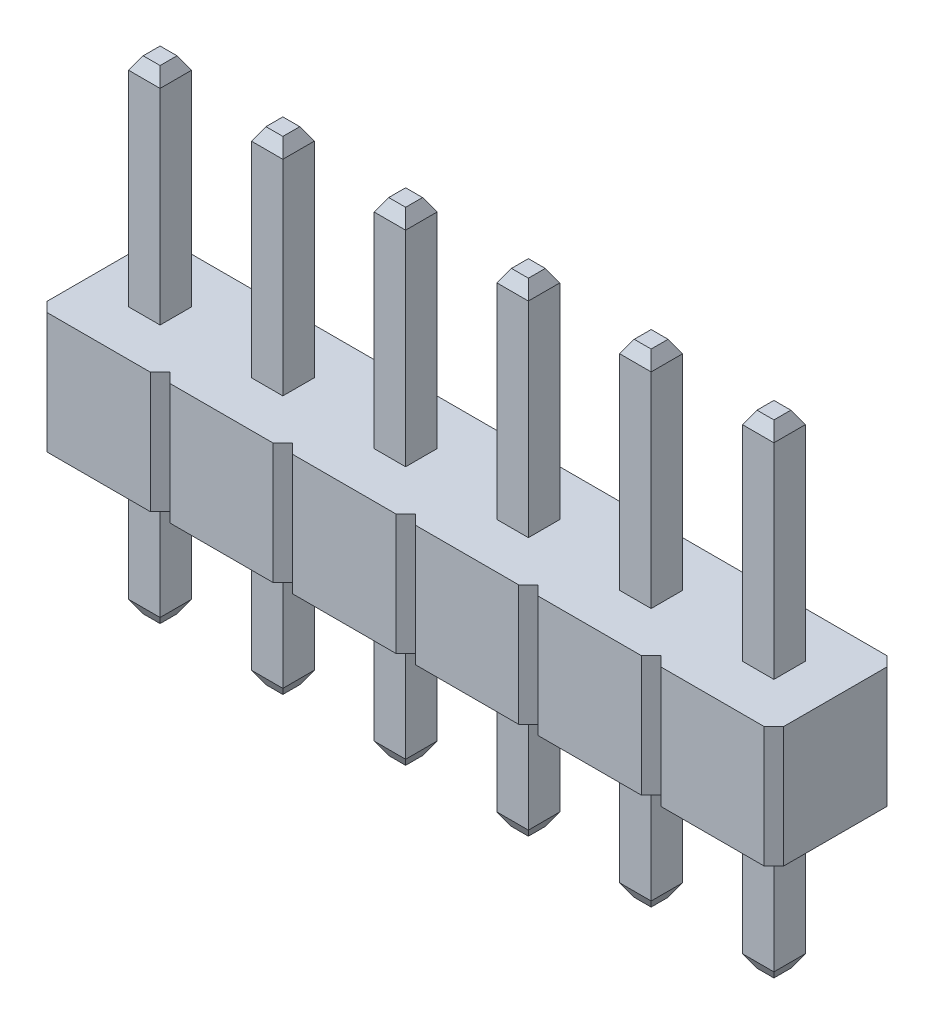
SolidWorks part; units mm, degrees
ref_plane "Front Plane" through (0, 0, 0) normal (0, 0, 1) x (1, 0, 0)
ref_plane "Top Plane" through (0, 0, 0) normal (0, 1, 0) x (1, 0, 0)
ref_plane "Right Plane" through (0, 0, 0) normal (1, 0, 0) x (0, 0, -1)
sketch "Sketch1" plane through (0, 0, 0) normal (0, 1, 0) x (1, 0, 0)
  line L0 (-7.42, 1.27) -> (-7.62, 1.07)
  line L1 (-7.62, 1.27) -> (7.62, 1.27) construction
  line L2 (-7.62, 1.27) -> (-7.62, -1.27) construction
  line L3 (-7.62, -1.27) -> (7.62, -1.27) construction
  line L4 (7.62, 1.27) -> (7.62, -1.27) construction
  line L5 (-7.62, 1.27) -> (7.62, -1.27) construction
  line L6 (-7.62, -1.27) -> (7.62, 1.27) construction
  line L7 (-5.28, -1.27) -> (-7.42, -1.27)
  line L8 (-5.08, -1.07) -> (-5.08, 1.07)
  line L9 (-5.28, 1.27) -> (-7.42, 1.27)
  line L10 (-7.62, -1.07) -> (-7.62, 1.07)
  line L11 (-5.08, -1.27) -> (-7.62, 1.27) construction
  line L12 (-5.08, 1.27) -> (-7.62, -1.27) construction
  line L13 (-5.08, 1.07) -> (-5.28, 1.27)
  line L14 (-7.42, -1.27) -> (-7.62, -1.07)
  line L15 (-5.08, -1.07) -> (-5.28, -1.27)
  point P0 (0, 0)
  point P6 (-6.35, 0)
  dimension "D1" = 15.24
  dimension "D2" = 2.54
extrude "Boss-Extrude1" add sketch "Sketch1" along normal blind 2.5
ref_plane "Plane1" through (0, -3, 0) normal (0, 1, 0) x (1, 0, 0)
sketch "Sketch3" plane through (0, -3, 0) normal (0, 1, 0) x (1, 0, 0)
  line L0 (-7.52, -1.17) -> (-5.18, 1.17) construction
  line L1 (-7.62, -1.07) -> (-7.42, -1.27) construction
  line L2 (-5.08, 1.07) -> (-5.28, 1.27) construction
  line L4 (-6.675, 0.325) -> (-6.025, 0.325)
  line L5 (-6.675, 0.325) -> (-6.675, -0.325)
  line L6 (-6.675, -0.325) -> (-6.025, -0.325)
  line L7 (-6.025, 0.325) -> (-6.025, -0.325)
  line L8 (-6.675, 0.325) -> (-6.025, -0.325) construction
  line L9 (-6.675, -0.325) -> (-6.025, 0.325) construction
  circle A0 centre (-6.35, 0) radius 0.325 construction
  dimension "D1" = 0.65
extrude "Boss-Extrude2" add sketch "Sketch3" along normal blind 10
chamfer "Chamfer2" distance 0.15 angle 60 4 edges at (-6.35, -3, -0.325) (-6.675, -3, 0) (-6.35, -3, 0.325) (-6.025, -3, 0)
ref_plane "Plane2" through (0, 1.25, 0) normal (0, -1, 0) x (-1, 0, 0)
chamfer "Chamfer3" distance 0.15 angle 60 4 edges at (-6.35, 7, 0.325) (-6.675, 7, 0) (-6.35, 7, -0.325) (-6.025, 7, 0)
pattern_linear "LPattern2" count 6 spacing 2.54 along (1, 0, 0) of "Boss-Extrude1", "Boss-Extrude2", "Chamfer2", "Chamfer3"
